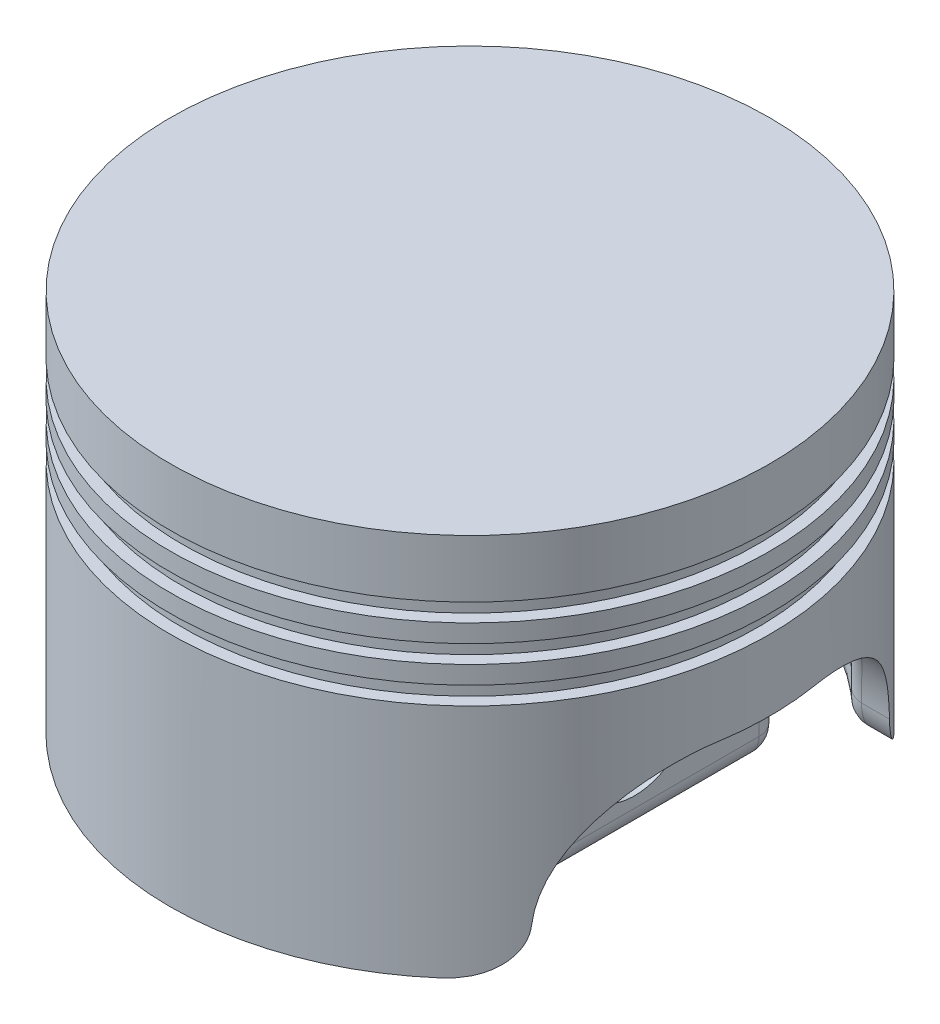
SolidWorks part; units mm, degrees
ref_plane "Front Plane" through (0, 0, 0) normal (0, 0, 1) x (1, 0, 0)
ref_plane "Top Plane" through (0, 0, 0) normal (0, 1, 0) x (1, 0, 0)
ref_plane "Right Plane" through (0, 0, 0) normal (1, 0, 0) x (0, 0, -1)
sketch "Sketch1" plane through (0, 0, 0) normal (0, 0, 1) x (1, 0, 0)
  line L0 (0, 81.28) -> (63.5, 81.28)
  line L14 (0, 62.28) -> (57.15, 62.28)
  line L16 (57.15, 0) -> (63.5, 0)
  line L17 (0, 81.28) -> (0, 62.28)
  line L18 (63.5, 81.28) -> (63.5, 69.05)
  line L19 (63.5, 69.05) -> (60.96, 69.05)
  line L20 (60.96, 69.05) -> (60.96, 65.24)
  line L21 (60.96, 65.24) -> (63.5, 65.24)
  line L22 (63.5, 65.24) -> (63.5, 61.43)
  line L23 (63.5, 61.43) -> (60.96, 61.43)
  line L24 (60.96, 61.43) -> (60.96, 57.62)
  line L25 (60.96, 57.62) -> (63.5, 57.62)
  line L26 (63.5, 57.62) -> (63.5, 53.81)
  line L27 (63.5, 53.81) -> (60.96, 53.81)
  line L28 (60.96, 53.81) -> (60.96, 50)
  line L29 (60.96, 50) -> (63.5, 50)
  line L30 (63.5, 50) -> (63.5, 0)
  line L31 (57.15, 0) -> (57.15, 62.28)
  line L32 (0, 0) -> (0, 62.28) construction
  dimension "D1" = 19
  dimension "D2" = 3.81
  dimension "D3" = 81.28
  dimension "D4" = 3.81
  dimension "D5" = 3.81
  dimension "D6" = 19.05
  dimension "D7" = 3.81
  dimension "D8" = 6.35
  dimension "D9" = 2.54
  dimension "D10" = 63.5
  dimension "D11" = 2.54
  dimension "D12" = 2.54
  dimension "D13" = 2.54
  dimension "D14" = 2.54
  dimension "D15" = 50
revolve "Revolve1" add sketch "Sketch1" angle 360 about L32
sketch "Sketch2" plane through (0, 0, 0) normal (1, 0, 0) x (0, 0, -1)
  line L0 (0, 0) -> (0, 30) construction
  line L1 (10, 35) -> (-10, 35)
  line L2 (-38, 7) -> (-38, 0)
  line L3 (-63.5, 0) -> (63.5, 0) construction
  line L4 (-38, 0) -> (38, 0)
  line L5 (38, 0) -> (38, 7)
  arc A0 (-10, 35) -> (-38, 7) centre (-10, 7) ccw
  arc A1 (38, 7) -> (10, 35) centre (10, 7) ccw
  point P6 (0, 30)
  point P13 (-38, 35)
  point P16 (38, 35)
  dimension "D3" = 28
  dimension "D4" = 28
  dimension "D1" = 35
  dimension "D2" = 76
  dimension "D5" = 38
extrude "Cut-Extrude1" cut sketch "Sketch2" against normal blind 110 and the other way blind 95 contours A0 L2 L4 L5 A1 L1
fillet "Fillet1" radius 10 4 edges at (-46.7806, 0, -38) (46.7806, 0, -38) (-46.7806, 0, 38) (46.7806, 0, 38)
sketch "Sketch3" plane through (0, 0, 0) normal (1, 0, 0) x (0, 0, -1)
  line L0 (-31.3471, 62.28) -> (-31.3471, -1.22)
  line L2 (0, 0) -> (0, 83.5896) construction
  line L3 (31.3471, 62.28) -> (31.3471, -1.22)
  line L4 (-31.3471, 62.28) -> (31.3471, 62.28)
  line L5 (63.5, 81.28) -> (-63.5, 81.28) construction
  line L6 (-31.3471, -1.22) -> (31.3471, -1.22)
  circle A0 centre (0, 18.78) radius 12.7
  dimension "D3" = 25.4
  dimension "D1" = 19
  dimension "D2" = 63.5
  dimension "D4" = 20
extrude "Boss-Extrude1" add sketch "Sketch3" along normal mid plane 19 from offset 25.38
fillet "Fillet2" radius 5 12 edges at (34.88, 62.28, 0) (15.88, 62.28, 0) (34.88, -1.22, 0) (15.88, -1.22, 0) (25.38, 62.28, 31.3471) (34.88, 30.53, 31.3471) (25.38, -1.22, 31.3471) (15.88, 30.53, 31.3471) (25.38, -1.22, -31.3471) (34.88, 30.53, -31.3471) (25.38, 62.28, -31.3471) (15.88, 30.53, -31.3471)
mirror "Mirror2" about plane through (0, 0, 0) normal (1, 0, 0) of "Fillet2", "Boss-Extrude1"
fillet "Fillet3" radius 5 13 edges at (-57.15, 35, 0) (-46.1361, 21.8654, 33.728) (-40.2071, 3.1307, 40.6141) (0, 0, 57.15) (41.1177, 4.2612, 39.692) (50.4876, 29.4156, 26.7792) (57.15, 35, 0) (46.1361, 21.8654, -33.728) (40.2071, 3.1307, -40.6141) (0, 0, -57.15) (-41.1177, 4.2612, -39.692) (-50.4876, 29.4156, -26.7792) (0, 62.28, -57.15)
